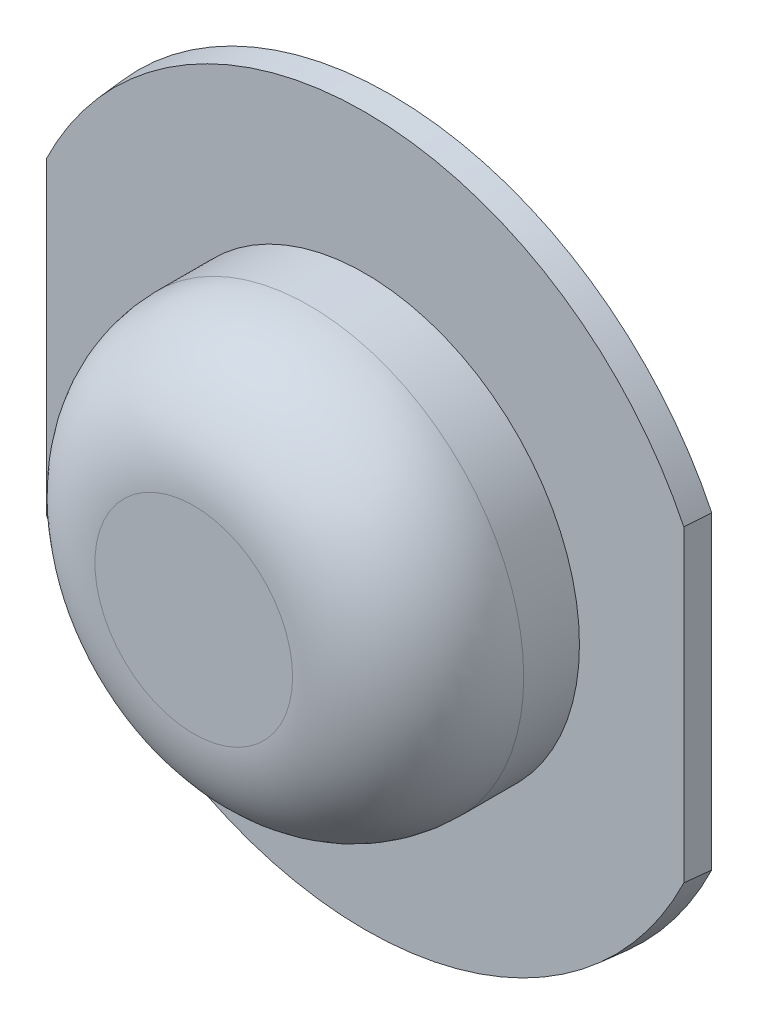
SolidWorks part; units mm, degrees
material "Silicon"
ref_plane "Front Plane" through (0, 0, 0) normal (0, 0, 1) x (1, 0, 0)
ref_plane "Top Plane" through (0, 0, 0) normal (0, 1, 0) x (1, 0, 0)
ref_plane "Right Plane" through (0, 0, 0) normal (1, 0, 0) x (0, 0, -1)
ref_axis "Axis1" through (0, 0, 0) along (0, 0, 1)
sketch "Sketch1" plane through (0, 0, 0) normal (0, 0, 1) x (1, 0, 0)
  line L0 (50, 24.0884) -> (50, -24.0884)
  line L1 (-50, 24.0884) -> (-50, -24.0884)
  arc A0 (-50, -24.0884) -> (50, -24.0884) centre (0, 0) ccw
  arc A1 (50, 24.0884) -> (-50, 24.0884) centre (0, 0) ccw
  dimension "D1" = 55.5
  dimension "D2" = 100
extrude "Boss-Extrude1" add sketch "Sketch1" along normal blind 4 draft 5
sketch "Sketch5" plane through (0, 0, 0) normal (0, 0, 1) x (1, 0, 0)
  line L0 (0, 0) -> (0, -41.75) construction
  line L1 (43.25, 43.25) -> (-43.25, 43.25) construction
  line L2 (43.25, 43.25) -> (43.25, -43.25) construction
  line L3 (43.25, -43.25) -> (-43.25, -43.25) construction
  line L4 (-43.25, 43.25) -> (-43.25, -43.25) construction
  line L5 (43.25, 43.25) -> (-43.25, -43.25) construction
  line L6 (43.25, -43.25) -> (-43.25, 43.25) construction
  line L7 (0, 0) -> (0, 41.75) construction
  line L8 (0, 0) -> (-41.75, 0) construction
  line L9 (0, 0) -> (41.75, 0) construction
  line L11 (-36, 36) -> (36, 36) construction
  line L12 (-36, 36) -> (-36, -36) construction
  line L13 (-36, -36) -> (36, -36) construction
  line L14 (36, 36) -> (36, -36) construction
  line L15 (-36, 36) -> (36, -36) construction
  line L16 (-36, -36) -> (36, 36) construction
  circle A0 centre (18.497, -18.497) radius 24.753 construction
  circle A1 centre (-18.497, -18.497) radius 24.753 construction
  circle A2 centre (18.497, 18.497) radius 24.753 construction
  circle A3 centre (-18.497, 18.497) radius 24.753 construction
  spline S0 degree 3 poles (45.3558, 18.4579) (39.9657, 0) (45.3558, -18.4579) (38.0677, -38.0677) (18.4579, -45.3558) (0, -39.9657) (-18.4579, -45.3558) (-38.0677, -38.0677) (-45.3558, -18.4579) (-39.9657, 0) (-45.3558, 18.4579) (-38.0677, 38.0677) (-18.4579, 45.3558) (0, 39.9657) (18.4579, 45.3558) (38.0677, 38.0677) (45.3558, 18.4579) (39.9657, 0) (45.3558, -18.4579) knots -0.188146 -0.125 -0.061854 0 0.061854 0.125 0.188146 0.25 0.311854 0.375 0.438146 0.5 0.561854 0.625 0.688146 0.75 0.811854 0.875 0.938146 1 1.061854 1.125 1.188146 only from (41.75, 0) to (41.75, 0)
  point P0 (0, 0)
  dimension "D1" = 86.5
  dimension "D2" = 83.5
  dimension "D3" = 72
extrude "Boss-Extrude2" [suppressed] add sketch "Sketch5" along normal blind 29.78 draft 4
fillet "Fillet1" [suppressed] radius 12
sketch "Sketch6" plane through (0, 0, 0) normal (0, 0, -1) x (-1, 0, 0)
  line L1 (-26.27, -26.27) -> (26.27, -26.27)
  line L2 (-26.27, -26.27) -> (-26.27, 26.27)
  line L3 (-26.27, 26.27) -> (26.27, 26.27)
  line L4 (26.27, -26.27) -> (26.27, 26.27)
  line L5 (-26.27, -26.27) -> (26.27, 26.27) construction
  line L6 (-26.27, 26.27) -> (26.27, -26.27) construction
  point P0 (0, 0)
  dimension "D1" = 52.54
extrude "Cut-Extrude2" cut sketch "Sketch6" against normal blind 2.35
sketch "Sketch7" plane through (0, 0, 0) normal (0, 1, 0) x (1, 0, 0)
  line L0 (0, -2.35) -> (0, -27.35)
  line L1 (26.27, -2.35) -> (-26.27, -2.35) construction
  line L2 (0, -2.35) -> (25, -2.35)
  arc A0 (0, -27.35) -> (25, -2.35) centre (0, -2.35) ccw
  dimension "D1" = 25
revolve "Cut-Revolve1" cut sketch "Sketch7" angle 360 about L0
sketch "Sketch8" plane through (0, 0, 2.35) normal (0, 0, -1) x (-1, 0, 0)
  line L0 (19.5512, 19.5512) -> (-19.5512, -19.5512) construction
  line L1 (-26.27, 26.27) -> (-26.27, -26.27) construction
  line L3 (-19.887, -15.1494) -> (-15.1494, -19.887)
  line L4 (-19.887, -15.1494) -> (-22.5387, -17.8011)
  line L5 (-22.5387, -20.6295) -> (-20.6295, -22.5387)
  line L6 (-15.1494, -19.887) -> (-17.8011, -22.5387)
  line L7 (-19.887, -15.1494) -> (-19.2153, -23.9529) construction
  line L8 (-23.9529, -19.2153) -> (-15.1494, -19.887) construction
  circle A0 centre (0, 0) radius 25 construction
  arc A1 (-22.5387, -17.8011) -> (-22.5387, -20.6295) centre (-21.1245, -19.2153) ccw
  arc A2 (-20.6295, -22.5387) -> (-17.8011, -22.5387) centre (-19.2153, -21.1245) ccw
  point P4 (0, 0)
  point P45 (0, 0)
  dimension "D4" = 2
  dimension "D1" = 45
  dimension "D2" = 5.75
  dimension "D3" = 6.7
extrude "Cut-Extrude3" cut sketch "Sketch8" against normal blind 0.8
pattern_circular "CirPattern1" count 4 over 360 about axis through (0, 0, 0) along (0, 0, 1) of "Cut-Extrude3"
sketch "Sketch9" plane through (0, 0, 4) normal (0, 0, 1) x (1, 0, 0)
  circle A0 centre (0, 0) radius 33.395
  dimension "D1" = 66.79
extrude "Boss-Extrude3" add sketch "Sketch9" along normal blind 26.68
fillet "Fillet2" radius 18 1 edges at (33.395, 0, 30.68)
